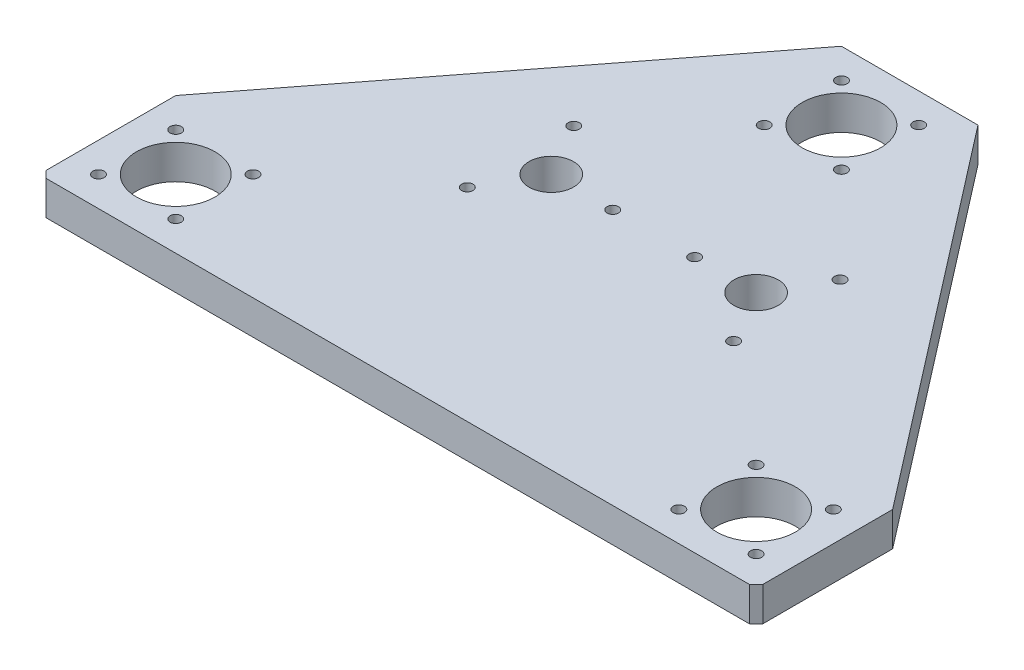
SolidWorks part; units mm, degrees
ref_plane "Front Plane" through (0, 0, 0) normal (0, 0, 1) x (1, 0, 0)
ref_plane "Top Plane" through (0, 0, 0) normal (0, 1, 0) x (1, 0, 0)
ref_plane "Right Plane" through (0, 0, 0) normal (1, 0, 0) x (0, 0, -1)
sketch "Sketch1" plane through (0, 0, 0) normal (0, 1, 0) x (1, 0, 0)
  line L0 (0, 0) -> (0, 55) construction
  line L1 (0, 0) -> (-85, -55) construction
  line L2 (0, 0) -> (85, -55) construction
  line L3 (0, 0) -> (-30, 0) construction
  line L4 (0, 0) -> (30, 0) construction
  line L5 (-105, -35) -> (-20, 75)
  line L6 (-65, -75) -> (-105, -75)
  line L7 (-65, -75) -> (-65, -35) construction
  line L8 (-65, -35) -> (-105, -35) construction
  line L9 (-105, -75) -> (-105, -35)
  line L10 (-65, -75) -> (-105, -35) construction
  line L11 (-65, -35) -> (-105, -75) construction
  line L12 (105, -75) -> (65, -75)
  line L13 (105, -75) -> (105, -35)
  line L14 (105, -35) -> (65, -35) construction
  line L15 (65, -75) -> (65, -35) construction
  line L16 (105, -75) -> (65, -35) construction
  line L17 (105, -35) -> (65, -75) construction
  line L18 (20, 35) -> (-20, 35) construction
  line L19 (20, 35) -> (20, 75) construction
  line L20 (20, 75) -> (-20, 75)
  line L21 (-20, 35) -> (-20, 75) construction
  line L22 (20, 35) -> (-20, 75) construction
  line L23 (20, 75) -> (-20, 35) construction
  line L24 (20, 75) -> (105, -35)
  line L25 (-65, -75) -> (65, -75)
  circle A0 centre (-30, 0) radius 6.5
  circle A1 centre (30, 0) radius 6.5
  circle A2 centre (0, 55) radius 11.5
  circle A3 centre (85, -55) radius 11.5
  circle A4 centre (-85, -55) radius 11.5
  circle A5 centre (-30, 0) radius 20 construction
  circle A6 centre (30, 0) radius 20 construction
  dimension "D5" = 13
  dimension "D6" = 23
  dimension "D8" = 40
  dimension "D1" = 55
  dimension "D2" = 55
  dimension "D3" = 85
  dimension "D4" = 60
  dimension "D7" = 40
extrude "Boss-Extrude1" add sketch "Sketch1" along normal blind 10
chamfer "Chamfer1" distance 2 angle 45 2 edges at (105, 5, 75) (-105, 5, 75)
sketch "Sketch2" plane through (0, 10, 0) normal (0, 1, 0) x (1, 0, 0)
  line L0 (-30, 0) -> (-12, 0) construction
  line L2 (11.3137, 43.6863) -> (-11.3137, 43.6863)
  line L3 (11.3137, 43.6863) -> (11.3137, 66.3137)
  line L4 (11.3137, 66.3137) -> (-11.3137, 66.3137)
  line L5 (-11.3137, 43.6863) -> (-11.3137, 66.3137)
  line L6 (11.3137, 43.6863) -> (-11.3137, 66.3137) construction
  line L7 (11.3137, 66.3137) -> (-11.3137, 43.6863) construction
  line L8 (-73.6863, -66.3137) -> (-96.3137, -66.3137)
  line L9 (-73.6863, -66.3137) -> (-73.6863, -43.6863)
  line L10 (-73.6863, -43.6863) -> (-96.3137, -43.6863)
  line L11 (-96.3137, -66.3137) -> (-96.3137, -43.6863)
  line L12 (-73.6863, -66.3137) -> (-96.3137, -43.6863) construction
  line L13 (-73.6863, -43.6863) -> (-96.3137, -66.3137) construction
  point P2 (0, 55)
  point P3 (-12, 0)
  point P11 (-85, -55)
  dimension "D1" = 32
  dimension "D2" = 32
  dimension "D3" = 18
hole_wizard "M4x0.7 Tapped Hole1" positions "3DSketch1" profile "Sketch3" tap size "M4x0.7" standard "BSI" end condition through all
sketch3d "3DSketch1"
  point P0 (-96.3137, 10, 43.6863)
  point P3 (-73.6863, 10, 43.6863)
  point P6 (-73.6863, 10, 66.3137)
  point P9 (-96.3137, 10, 66.3137)
  point P15 (-11.3137, 10, -43.6863)
  point P18 (-11.3137, 10, -66.3137)
  point P23 (0, 0, 0)
sketch "Sketch3" plane through (-96.3137, 10, 43.6863) normal (1, 0, 0) x (0, 0, 1)
  line L0 (0, 0) -> (0, 10)
  line L1 (0, 10) -> (1.65, 10)
  line L2 (1.65, 10) -> (1.65, 0)
  line L5 (1.65, 0) -> (0, 0)
  line L11 (0, -6.35) -> (0, 107.95) construction
  dimension "Thru Tap Drill Dia." = 3.3
  dimension "Thru Tap Drill Depth" = 10
cosmetic thread "Hole Thread1" parameters "D2"=4
cosmetic thread "Hole Thread2" parameters "D2"=4
cosmetic thread "Hole Thread4" parameters "D2"=4
cosmetic thread "Hole Thread5" parameters "D2"=4
cosmetic thread "Hole Thread6" parameters "D2"=4
cosmetic thread "Hole Thread7" parameters "D2"=4
hole_wizard "M4x0.7 Tapped Hole2" positions "3DSketch2" profile "Sketch4" tap size "M4x0.7" standard "BSI" end condition through all
sketch3d "3DSketch2"
  point P0 (-12, 10, 0)
sketch "Sketch4" plane through (-12, 10, 0) normal (1, 0, 0) x (0, 0, 1)
  line L0 (0, 0) -> (0, 10)
  line L1 (0, 10) -> (1.65, 10)
  line L2 (1.65, 10) -> (1.65, 0)
  line L5 (1.65, 0) -> (0, 0)
  line L11 (0, -6.35) -> (0, 107.95) construction
  dimension "Thru Tap Drill Dia." = 3.3
  dimension "Thru Tap Drill Depth" = 10
cosmetic thread "Hole Thread8" parameters "D2"=4
pattern_circular "CirPattern1" count 3 over 360 about axis through (-30, 10, 0) along (0, -1, 0) of "M4x0.7 Tapped Hole2"
cosmetic thread "Hole Thread9" parameters "D2"=4
cosmetic thread "Hole Thread10" parameters "D2"=4
mirror "Mirror1" about plane through (0, 0, 0) normal (1, 0, 0) of "CirPattern1", "M4x0.7 Tapped Hole2", "M4x0.7 Tapped Hole1"
cosmetic thread "Hole Thread11" parameters "D2"=4
cosmetic thread "Hole Thread12" parameters "D2"=4
cosmetic thread "Hole Thread13" parameters "D2"=4
cosmetic thread "Hole Thread14" parameters "D2"=4
cosmetic thread "Hole Thread15" parameters "D2"=4
cosmetic thread "Hole Thread16" parameters "D2"=4
cosmetic thread "Hole Thread17" parameters "D2"=4
cosmetic thread "Hole Thread18" parameters "D2"=4
cosmetic thread "Hole Thread19" parameters "D2"=4
